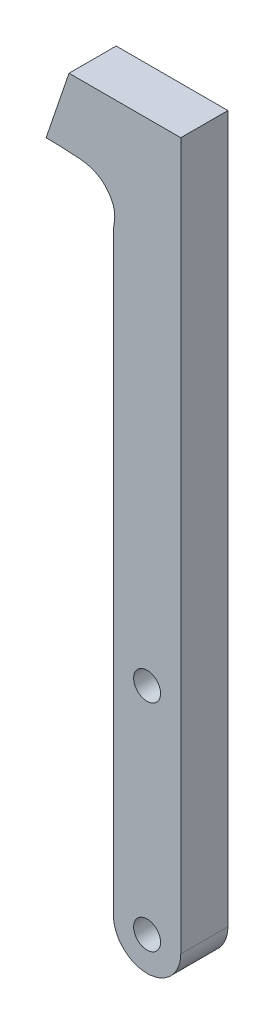
SolidWorks part; units mm, degrees
ref_plane "Plan de face" through (0, 0, 0) normal (0, 0, 1) x (1, 0, 0)
ref_plane "Plan de dessus" through (0, 0, 0) normal (0, 1, 0) x (1, 0, 0)
ref_plane "Plan de droite" through (0, 0, 0) normal (1, 0, 0) x (0, 0, -1)
sketch "Esquisse1" plane through (0, 0, 0) normal (0, 0, 1) x (1, 0, 0)
  line L0 (0, 0) -> (10, 0)
  line L1 (10, 0) -> (10, -52.5)
  line L2 (0, 0) -> (0, -5)
  line L3 (0, -5) -> (5, -5)
  line L4 (5, -5) -> (5, -52.5)
  arc A0 (5, -52.5) -> (10, -52.5) centre (7.5, -52.5) ccw
  point P8 (7.5, -55)
  point P9 (2.5, -5)
  dimension "D1" = 50
  dimension "D2" = 10
  dimension "D3" = 5
  dimension "D4" = 5
extrude "Boss.-Extru.1" add sketch "Esquisse1" along normal blind 3.5
sketch "Esquisse3" plane through (0, 0, 0) normal (0, 0, -1) x (-1, 0, 0)
  line L0 (-10, -52.5) -> (-5, -52.5) construction
  arc A0 (-10, -52.5) -> (-5, -52.5) centre (-7.5, -52.5) ccw construction
  circle A1 centre (-7.5, -52.5) radius 1
  dimension "D1" = 2
extrude "Enlèv. mat.-Extru.1" cut sketch "Esquisse3" against normal blind 4
sketch "Esquisse4" plane through (0, 0, 3.5) normal (0, 0, 1) x (1, 0, 0)
  line L0 (7.5, -51.5) -> (7.5, -36.5) construction
  circle A0 centre (7.5, -52.5) radius 1 construction
  circle A1 centre (7.5, -36.5) radius 1
  dimension "D2" = 2
  dimension "D1" = 15
extrude "Enlèv. mat.-Extru.2" cut sketch "Esquisse4" against normal blind 10
sketch "Esquisse5" plane through (0, 0, 3.5) normal (0, 0, 1) x (1, 0, 0)
  line L0 (0, 0) -> (1.7009, 0)
  line L1 (10, 0) -> (0, 0) construction
  line L2 (1.7009, 0) -> (0, -5)
  line L3 (0, -5) -> (0, 0)
extrude "Enlèv. mat.-Extru.3" cut sketch "Esquisse5" against normal through all
fillet "Congé1" radius 5 1 edges at (5, -5, 1.75)
sketch "Esquisse11" plane through (0, 0, 3.5) normal (0, 0, 1) x (1, 0, 0)
  line L0 (5.1434, -7.3057) -> (4.9822, -8.5099)
  line L1 (4.9822, -8.5099) -> (2.0308, -5.0809)
  spline S0 degree 2 poles (2.0308, -5.0809) (4.5437, -5.0648) (5.1434, -7.3057) knots 0 0 0 1 1 1
  spline S1 degree 2 poles (0, -5) (0.9836, -5) (1.7028, -5.0527) (2.7407, -5.1288) (3.3793, -5.3295) (3.8378, -5.4735) (4.1469, -5.6966) (4.4993, -5.9511) (4.6971, -6.3386) (5, -6.9321) (5, -8) knots 0 0 0 0.25 0.25 0.5 0.5 0.625 0.625 0.75 0.75 1 1 1 construction
  point P2 (2.861, -4.9668)
  point P5 (4.5796, -6.0374)
  point P6 (5.1434, -7.3057)
  point P7 (4.3758, -5.8922)
  point P10 (2.0308, -5.0809)
extrude "Enlèv. mat.-Extru.7" cut sketch "Esquisse11" against normal blind 6
fillet "Congé4" radius 2 2 edges at (5, -8.3772, 1.75) (5.1434, -7.3057, 1.75)
fillet "Congé5" radius 2 1 edges
